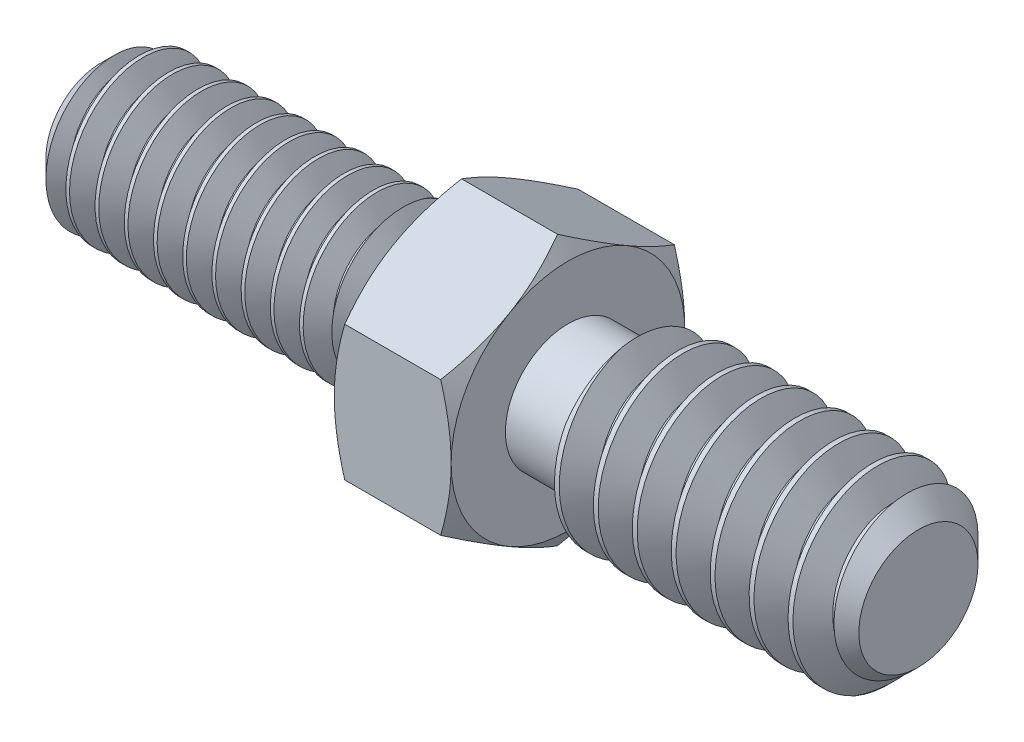
SolidWorks part; units mm, degrees
ref_plane "Front Plane" through (0, 0, 0) normal (0, 0, 1) x (1, 0, 0)
ref_plane "Top Plane" through (0, 0, 0) normal (0, 1, 0) x (1, 0, 0)
ref_plane "Right Plane" through (0, 0, 0) normal (1, 0, 0) x (0, 0, -1)
sketch "Sketch1" plane through (0, 0, 0) normal (0, 0, 1) x (1, 0, 0)
  line L0 (-11.1125, 0) -> (11.1125, 0) construction
  line L1 (0, 3.175) -> (0, -3.175) construction
  line L2 (-11.1125, 2.0828) -> (-11.1125, -2.0828) construction
  line L3 (11.1125, 2.413) -> (11.1125, -2.413) construction
  line L4 (-1.5875, 3.175) -> (1.5875, 3.175) construction
  line L5 (-1.5875, -3.175) -> (1.5875, -3.175) construction
  point P13 (-8.1359, -2.0828)
  point P14 (7.1437, -2.413)
  dimension "Hex" = 6.35
  dimension "A" = 3.175
  dimension "Male 1" = 4.1656
  dimension "Male 2" = 4.826
  dimension "Length 1" = 9.525
  dimension "Length 2" = 9.525
  dimension "D1" = 2.9766
  dimension "D2" = 3.9688
sketch "Sketch2" plane through (0, 0, 0) normal (1, 0, 0) x (0, 0, -1)
  circle A0 centre (0, 0) radius 2.0828
extrude "Extrude1" add sketch "Sketch2" against normal up to vertex (11.1125 mm away) up to point (-11.1125, 0, 0)
chamfer "Chamfer1" distance 0.5953 angle 45 1 edges at (-11.1125, 0, -2.0828)
sketch "Sketch5" plane through (-11.1125, 0, 0) normal (1, 0, 0) x (0, 0, -1)
  circle A1 centre (0, 0) radius 2.0828
  circle A2 centre (0, 0) radius 2.0828
  dimension "D1" = 0
curve "Helix/Spiral3" pitch 0.7937 height 12.7 turns 16 parameters "Pitch 1"=0.7937
sketch "Sketch9" plane through (0, 0, 0) normal (0, 0, 1) x (1, 0, 0)
  line L0 (-10.8645, 2.0828) -> (-10.1699, 2.0828)
  line L1 (-10.8645, 2.0828) -> (-10.5668, 1.5672)
  line L2 (-10.5668, 1.5672) -> (-10.4676, 1.5672)
  line L3 (-10.4676, 1.5672) -> (-10.1699, 2.0828)
  line L4 (-10.5172, 1.5672) -> (-10.5172, 2.0828) construction
  line L5 (-10.7156, 1.825) -> (-10.3188, 1.825) construction
  dimension "D1" = 0.0992
  dimension "D2" = 0.3969
  dimension "D3" = 60
sweep "Cut-Sweep3" cut profiles "Sketch9" path "Helix/Spiral3" align with end faces yes
sketch "Sketch11" plane through (0, 0, 0) normal (0, 0, 1) x (1, 0, 0)
  line L0 (0, 2.0828) -> (0, 1.5164)
  line L1 (0, 1.5164) -> (-2.7424, 1.5164)
  line L2 (-2.7424, 1.5164) -> (-2.7424, 2.0828)
  line L3 (0, 2.0828) -> (-2.7424, 2.0828)
  line L4 (0.0445, 0) -> (-1.5626, 0) construction
  line L5 (0, 3.175) -> (0, -3.175) construction
  line L6 (-10.8645, 2.0828) -> (-10.1699, 2.0828) construction
  dimension "D2" = 2.7424
  dimension "D1" = 0.0508
revolve "Cut-Revolve1" cut sketch "Sketch11" angle 360 about L4
sketch "Sketch19" plane through (-2.7424, 0, 0) normal (1, 0, 0) x (0, 0, -1)
  circle A1 centre (0, 0) radius 1.5164
  circle A2 centre (0, 0) radius 1.5164
  dimension "D1" = 0
extrude "Extrude10" cut sketch "Sketch19" against normal through all draft 60 flip side to cut
sketch "Sketch3" plane through (0, 0, 0) normal (1, 0, 0) x (0, 0, -1)
  circle A0 centre (0, 0) radius 2.413
extrude "Extrude2" add sketch "Sketch3" along normal up to vertex (11.1125 mm away) separate body up to point (11.1125, 0, 0)
chamfer "Chamfer2" distance 0.7937 angle 45 1 edges at (11.1125, 0, -2.413)
sketch "Sketch4" plane through (11.1125, 0, 0) normal (1, 0, 0) x (0, 0, -1)
  circle A1 centre (0, 0) radius 2.413
curve "Helix/Spiral4" pitch 1.0583 height 12.7 turns 12 parameters "Pitch 2"=1.0583
sketch "Sketch10" plane through (0, 0, 0) normal (0, 0, 1) x (1, 0, 0)
  line L0 (9.8557, 2.413) -> (10.7818, 2.413)
  line L1 (9.8557, 2.413) -> (10.2526, 1.7256)
  line L2 (10.2526, 1.7256) -> (10.3849, 1.7256)
  line L3 (10.3849, 1.7256) -> (10.7818, 2.413)
  line L4 (10.3187, 1.7256) -> (10.3187, 2.413) construction
  line L5 (10.0542, 2.0693) -> (10.5833, 2.0693) construction
  dimension "D3" = 60
  dimension "D1" = 0.1323
  dimension "D2" = 0.5292
sweep "Cut-Sweep2" cut profiles "Sketch10" path "Helix/Spiral4" align with end faces yes
sketch "Sketch12" plane through (0, 0, 0) normal (0, 0, 1) x (1, 0, 0)
  line L1 (0, 1.7002) -> (3.1274, 1.7002)
  line L2 (3.1274, 1.7002) -> (3.1274, 2.413)
  line L3 (0, 2.413) -> (3.1274, 2.413)
  line L4 (-11.1125, -2.0828) -> (-11.1125, 2.0828) construction
  line L5 (-11.1125, 0) -> (3.1274, 0) construction
  line L6 (0, 3.175) -> (0, -3.175) construction
  line L7 (9.8557, 2.413) -> (10.7818, 2.413) construction
  line L8 (0, 1.7002) -> (0, 2.413)
  dimension "D3" = 3.1274
  dimension "D2" = 0.0254
revolve "Cut-Revolve2" cut sketch "Sketch12" angle 360 about L5
sketch "Sketch18" plane through (3.1274, 0, 0) normal (-1, 0, 0) x (0, 0, 1)
  circle A1 centre (0, 0) radius 1.7002
  circle A2 centre (0, 0) radius 1.7002
  dimension "D1" = 0
extrude "Extrude9" cut sketch "Sketch18" against normal through all draft 60 flip side to cut
sketch "Sketch6" plane through (0, 0, 0) normal (1, 0, 0) x (0, 0, -1)
  line L1 (0, 3.6662) -> (-3.175, 1.8331)
  line L2 (-3.175, 1.8331) -> (-3.175, -1.8331)
  line L3 (-3.175, -1.8331) -> (0, -3.6662)
  line L4 (0, -3.6662) -> (3.175, -1.8331)
  line L5 (3.175, -1.8331) -> (3.175, 1.8331)
  line L6 (3.175, 1.8331) -> (0, 3.6662)
  circle A0 centre (0, 0) radius 3.175 construction
extrude "Extrude3" add sketch "Sketch6" along normal up to vertex (1.5875 mm away) and the other way up to vertex (1.5875 mm away) up to point (1.5875, 3.175, 0) other way up to point (-1.5875, 3.175, 0)
sketch "Sketch13" plane through (-1.5875, 0, 0) normal (-1, 0, 0) x (0, 0, 1)
  circle A0 centre (0, 0) radius 3.175 construction
  circle A1 centre (0, 0) radius 3.175
extrude "Extrude4" cut sketch "Sketch13" against normal through all draft 60 flip side to cut
sketch "Sketch14" plane through (1.5875, 0, 0) normal (1, 0, 0) x (0, 0, -1)
  circle A0 centre (0, 0) radius 3.175 construction
  circle A1 centre (0, 0) radius 3.175
extrude "Extrude5" cut sketch "Sketch14" against normal through all draft 60 flip side to cut
equation "\"D3@Helix/Spiral3\"=\"Length 1@Sketch1\"+\"A@Sketch1\""
equation "\"D3@Helix/Spiral4\"=\"A@Sketch1\"+\"Length 2@Sketch1\""
equation "\"D1@Chamfer1\"=\"Pitch 1@Helix/Spiral3\"*.75"
equation "\"D1@Sketch9\"=\"Pitch 1@Helix/Spiral3\"*.125"
equation "\"D2@Sketch9\" = \"Pitch 1@Helix/Spiral3\"*.5"
equation "\"D1@Chamfer2\" = \"Pitch 2@Helix/Spiral4\"*.75"
equation "\"D1@Sketch10\" = \"Pitch 2@Helix/Spiral4\"*.125"
equation "\"D2@Sketch10\" =  \"Pitch 2@Helix/Spiral4\"*.5"
equation "\"D2@Sketch11\" =(\"A@Sketch1\"/2)+ (\"Pitch 1@Helix/Spiral3\"*1.455)"
equation "\"D3@Sketch12\" = (\"A@Sketch1\"/2)+(\"Pitch 2@Helix/Spiral4\"*1.455)"
equation "\"D1@Sketch1\" = \"Pitch 1@Helix/Spiral3\"*3.750"
equation "\"D2@Sketch1\" = \"Pitch 2@Helix/Spiral4\"*3.750"
